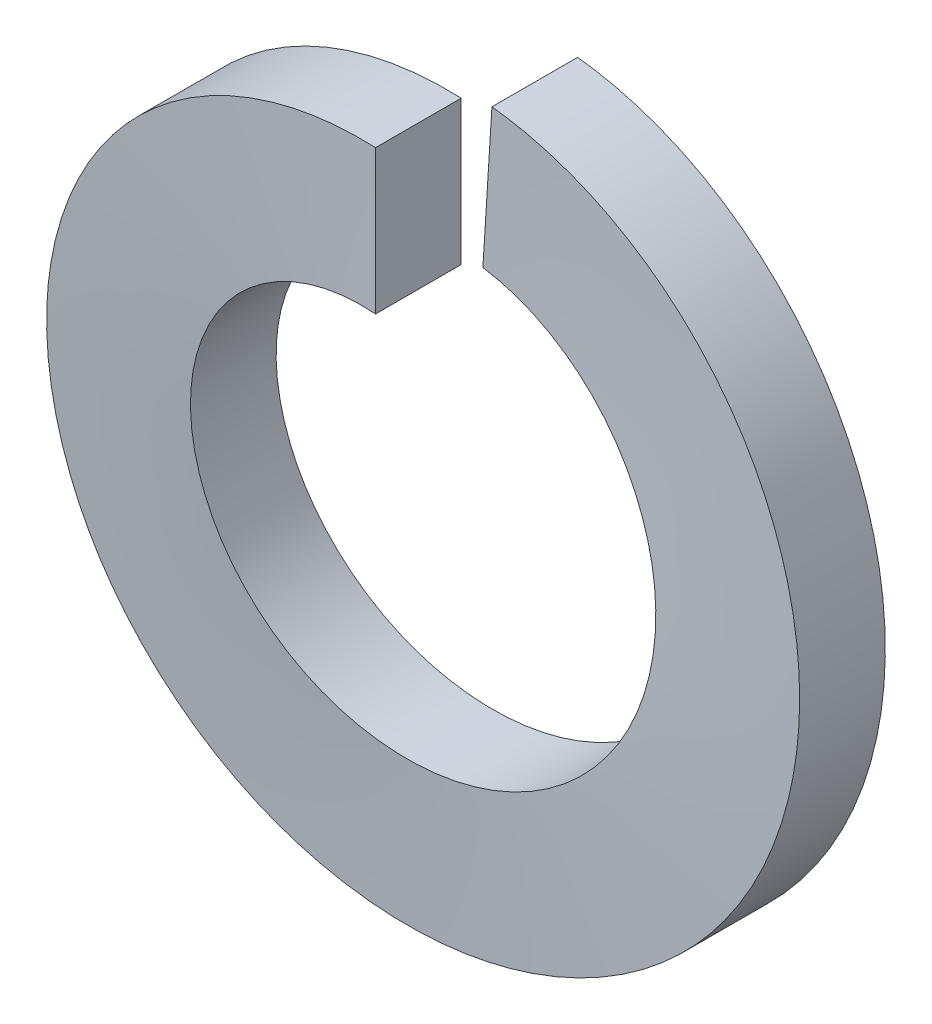
SolidWorks part; units mm, degrees
ref_plane "Front Plane" through (0, 0, 0) normal (0, 0, 1) x (1, 0, 0)
ref_plane "Top Plane" through (0, 0, 0) normal (0, 1, 0) x (1, 0, 0)
ref_plane "Right Plane" through (0, 0, 0) normal (1, 0, 0) x (0, 0, -1)
sketch "Spiral Sketch" plane through (0, 0, 0) normal (0, 0, 1) x (1, 0, 0)
  line L0 (0, 9.05) -> (0, 5.35) construction
  circle A0 centre (0, 0) radius 9.05
  circle A1 centre (0, 0) radius 5.35 construction
  dimension "ID" = 10.7
  dimension "OD" = 18.1
curve "Spiral" pitch 2.4444 height 2.42 radius 9.05 left hand yes centre (0, 0, 0) axis (0, 0, -1) start towards (0, 1, 0) parameters "HT"=2.42
sketch "Profile Sketch" plane through (0, 0, 0) normal (1, 0, 0) x (0, 0, -1)
  line L1 (0, 9.05) -> (-2.2, 9.05)
  line L2 (0, 9.05) -> (0, 5.35)
  line L3 (0, 5.35) -> (-2.2, 5.35)
  line L4 (-2.2, 9.05) -> (-2.2, 5.35)
  dimension "Thickness" = 2.2
sweep "Profile Sweep" add profiles "Profile Sketch" path "Spiral"
ref_axis "Center Axis 1" through (0, 0, -2.2957) along (0, 0, 1)
ref_plane "Contact Plane 1" through (0, 0, 2.2) normal (0, 0, 1) x (1, 0, 0)
ref_plane "Contact Plane 2" through (0, 0, -2.4206) normal (0, 0, 1) x (1, 0, 0)
equation "\"HT@Spiral\" = \"Thickness@Profile Sketch\" * 1.1"
